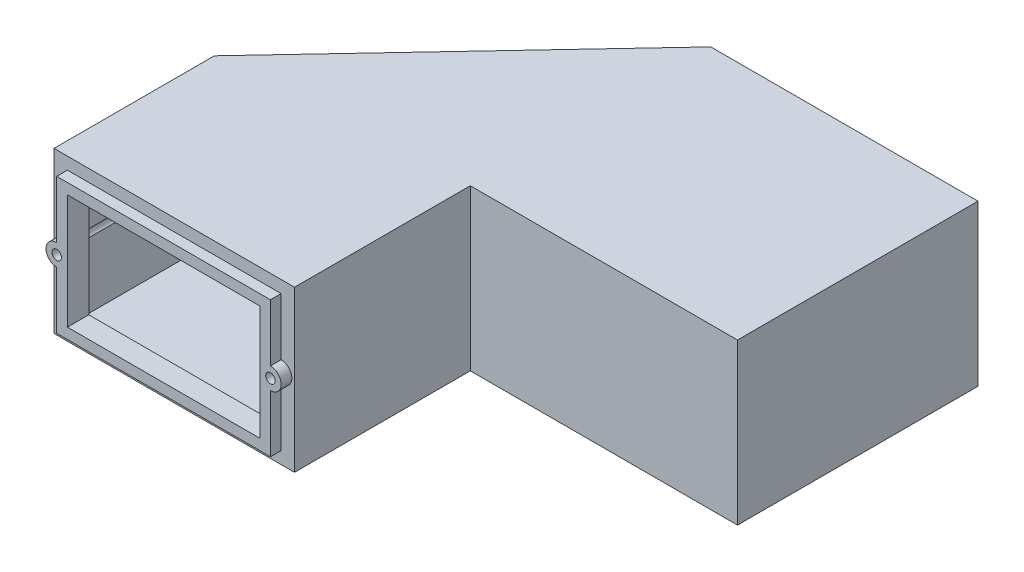
SolidWorks part; units mm, degrees
ref_plane "Front Plane" through (0, 0, 0) normal (0, 0, 1) x (1, 0, 0)
ref_plane "Top Plane" through (0, 0, 0) normal (0, 1, 0) x (1, 0, 0)
ref_plane "Right Plane" through (0, 0, 0) normal (1, 0, 0) x (0, 0, -1)
sketch "Sketch1" plane through (0, 0, 0) normal (0, 1, 0) x (1, 0, 0)
  line L0 (0, 0) -> (57.15, 0)
  line L1 (57.15, 0) -> (57.15, 41.777)
  line L4 (120.65, 98.927) -> (120.65, 41.777)
  line L5 (120.65, 41.777) -> (57.15, 41.777)
  line L6 (0, 38.1) -> (57.15, 98.927)
  line L7 (57.15, 98.927) -> (120.65, 98.927)
  line L8 (0, 38.1) -> (0, 0)
  dimension "D1" = 57.15
  dimension "D2" = 57.15
  dimension "D3" = 38.1
extrude "Boss-Extrude1" add sketch "Sketch1" along normal blind 38.1
ref_point "Point1"
sketch "Sketch3" plane through (0, 0, 0) normal (0, 0, 1) x (1, 0, 0)
  line L1 (3.175, 2.8956) -> (53.975, 2.8956)
  line L2 (3.175, 2.8956) -> (3.175, 35.2044)
  line L3 (3.175, 35.2044) -> (53.975, 35.2044)
  line L4 (53.975, 2.8956) -> (53.975, 35.2044)
  line L5 (3.175, 2.8956) -> (53.975, 35.2044) construction
  line L6 (3.175, 35.2044) -> (53.975, 2.8956) construction
  point P0 (28.575, 19.05)
  dimension "D1" = 50.8
  dimension "D2" = 32.3088
extrude "Boss-Extrude2" add sketch "Sketch3" along normal blind 2.54
shell "Shell2" thickness 2.54 removed face at (28.575, 19.05, 2.54)
sketch "Sketch5" plane through (0, 0, 2.54) normal (0, 0, 1) x (1, 0, 0)
  line L0 (3.175, 35.2044) -> (3.175, 2.8956) construction
  line L1 (53.975, 2.8956) -> (53.975, 35.2044) construction
  circle A0 centre (3.175, 19.05) radius 2.54
  circle A1 centre (53.975, 19.05) radius 2.54
  dimension "D1" = 5.08
  dimension "D2" = 5.08
extrude "Boss-Extrude3" add sketch "Sketch5" against normal up to surface (2.54 mm away) up to face at (28.575, 19.05, 0)
hole_wizard "#4-40 Tapped Hole1" positions "3DSketch1" profile "Sketch6" tap size "#4-40" standard "ANSI Inch"
sketch3d "3DSketch1"
  line L0 (3.175, 19.05, 0) -> (3.175, 19.05, 2.54) construction
  point P0 (53.975, 19.05, 2.54)
  point P2 (3.175, 19.05, 2.54)
  dimension "D1" = 50.8
sketch "Sketch6" plane through (53.975, 19.05, 2.54) normal (1, 0, 0) x (0, -1, 0)
  line L0 (0, 0) -> (0, 99.6052)
  line L1 (0, 99.6052) -> (1.1303, 98.926)
  line L2 (1.1303, 98.926) -> (1.1303, 0)
  line L5 (1.1303, 0) -> (0, 0)
  line L10 (0, 99.6052) -> (-1.1303, 98.926) construction
  line L11 (0, -6.35) -> (0, 107.95) construction
  dimension "Tap Drill Dia." = 2.2606
  dimension "Tap Drill Depth" = 98.926
  dimension "Drill Angle" = 118
sketch "centre of button" plane through (0, 0, -98.927) normal (0, 0, -1) x (-1, 0, 0)
  line L0 (-120.65, 0) -> (-57.15, 0) construction
  line L1 (-120.65, 38.1) -> (-120.65, 0) construction
  point P0 (-95.25, 19.05)
  dimension "D1" = 19.05
  dimension "D2" = 25.4
sketch "single button hole" plane through (0, 0, -98.927) normal (0, 0, -1) x (-1, 0, 0)
  line L0 (-93.345, 12.7) -> (-97.155, 12.7) construction
  line L1 (-93.345, 10.668) -> (-97.155, 10.668)
  line L2 (-93.345, 14.732) -> (-97.155, 14.732)
  arc A0 (-93.345, 10.668) -> (-93.345, 14.732) centre (-93.345, 12.7) ccw
  arc A1 (-97.155, 14.732) -> (-97.155, 10.668) centre (-97.155, 12.7) ccw
  point P3 (-95.25, 12.7)
  dimension "D3" = 2.032
  dimension "D1" = 3.81
  dimension "D2" = 0
  dimension "D4" = 6.35
extrude "Cut-Extrude1" cut sketch "single button hole" against normal blind 2.54
ref_axis "Axis1" through (95.25, 19.05, -98.927) along (0, 0, -1)
pattern_circular "CirPattern1" count 4 over 360 about axis through (95.25, 19.05, -98.927) along (0, 0, -1) of "Cut-Extrude1"
